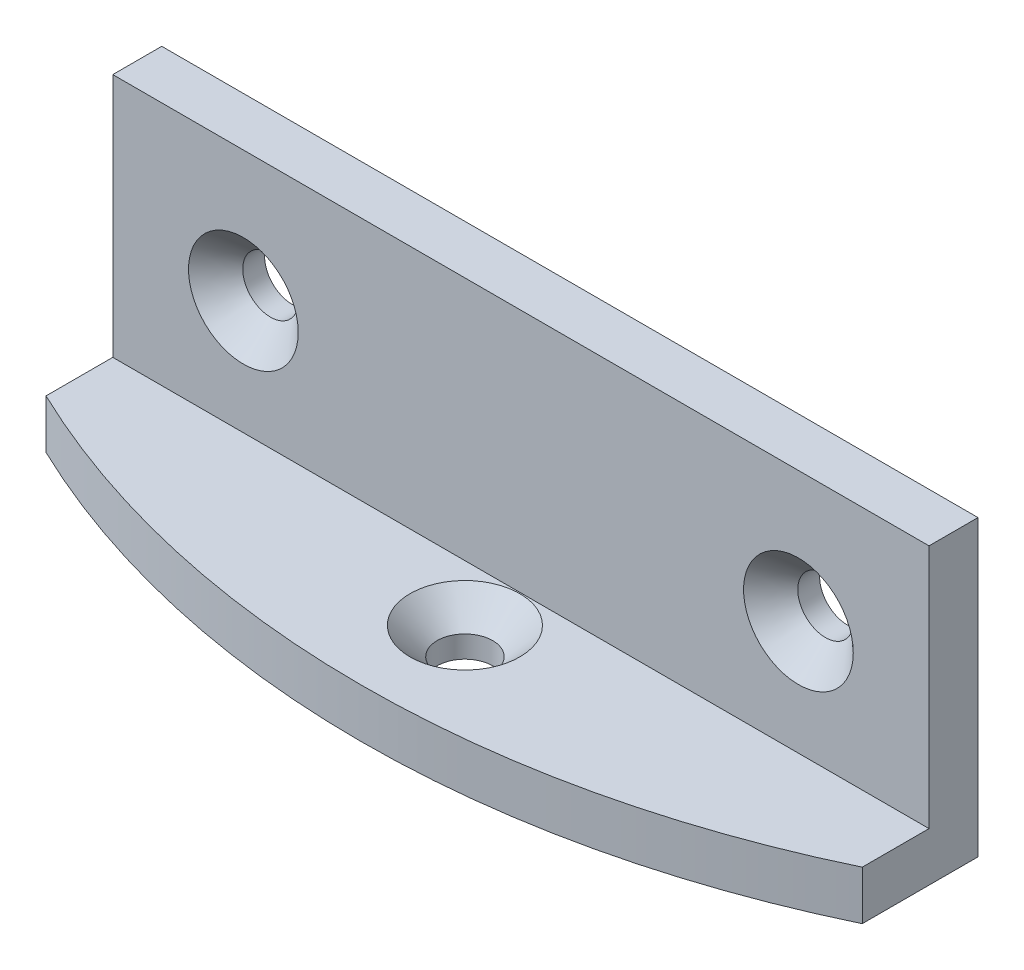
SolidWorks part; units mm, degrees
ref_plane "Plano frontal" through (0, 0, 0) normal (0, 0, 1) x (1, 0, 0)
ref_plane "Plano superior" through (0, 0, 0) normal (0, 1, 0) x (1, 0, 0)
ref_plane "Plano direito" through (0, 0, 0) normal (1, 0, 0) x (0, 0, -1)
sketch "Esboço2" plane through (0, 0, 0) normal (0, 1, 0) x (1, 0, 0)
  line L0 (-25, 0) -> (-25, -7.0901)
  line L1 (-25, 0) -> (25, 0)
  line L5 (25, 0) -> (25, -7.0901)
  arc A3 (-47.2548, 11.753) -> (-5.1654, -12.5473) centre (0, 45) ccw construction
  arc A4 (5.1654, -12.5473) -> (47.2548, 11.753) centre (0, 45) ccw construction
  arc A5 (-25, -7.0901) -> (25, -7.0901) centre (0, 45) ccw
  point P4 (0, 0)
  dimension "D1" = 50
extrude "Ressalto-extrusão1" add sketch "Esboço2" against normal blind 3 contours L1 L5 A5 L0
sketch "Esboço3" plane through (0, 0, 0) normal (0, 1, 0) x (1, 0, 0)
  line L1 (-25, 0) -> (25, 0)
  line L2 (-25, 0) -> (-25, -3)
  line L3 (-25, -3) -> (25, -3)
  line L4 (25, 0) -> (25, -3)
  line L5 (25, 0) -> (25, -7.0901) construction
  dimension "D1" = 3
extrude "Ressalto-extrusão2" add sketch "Esboço3" along normal blind 15
hole_wizard "Escareado para parafuso Allen sextavado escareado de M31" positions "Esboço4" profile "Esboço5" countersink size "M3" standard "ISO" end condition up to next
sketch "Esboço4" plane through (0, 0, 0) normal (0, 1, 0) x (1, 0, 0)
  point P0 (0, -6.4289)
sketch "Esboço5" plane through (0, 0, 6.4289) normal (1, 0, 0) x (0, 0, 1)
  line L0 (0, 0) -> (0, 3)
  line L1 (0, 3) -> (1.7, 3)
  line L2 (1.7, 3) -> (1.7, 1.66)
  line L3 (1.7, 1.66) -> (3.36, 0)
  line L5 (3.36, 0) -> (0, 0)
  line L6 (-1.7, 1.66) -> (-3.36, 0) construction
  line L11 (0, -6.35) -> (0, 107.95) construction
  dimension "Thru Hole Dia." = 3.4
  dimension "Thru Hole Depth" = 3
  dimension "Near C'Sink Dia." = 6.72
  dimension "Near C'Sink Angle" = 90
sketch "Esboço8" plane through (0, 0, 3) normal (0, 0, 1) x (1, 0, 0)
  line L0 (-25, 10) -> (-25, 4) construction
  line L1 (170, 10) -> (-170, 10) construction
  line L2 (170, 4) -> (-170, 4) construction
  line L3 (-25, 15) -> (-25, 0) construction
  line L4 (-25, 7) -> (25, 7) construction
  line L5 (25, 15) -> (25, 0) construction
hole_wizard "Escareado para parafuso Allen sextavado escareado de M33" positions "Esboço10" profile "Esboço11" countersink size "M3" standard "ISO" end condition up to next
sketch "Esboço10" plane through (0, 0, 3) normal (0, 0, 1) x (1, 0, 0)
  line L0 (-25, 7) -> (25, 7) construction
  line L1 (25, 15) -> (25, 0) construction
  point P0 (-17, 7)
  point P4 (17, 7)
  dimension "D1" = 8
  dimension "D2" = 8
sketch "Esboço11" plane through (-17, 7, 3) normal (1, 0, 0) x (0, -1, 0)
  line L0 (0, 0) -> (0, 3)
  line L1 (0, 3) -> (1.7, 3)
  line L2 (1.7, 3) -> (1.7, 1.66)
  line L3 (1.7, 1.66) -> (3.36, 0)
  line L5 (3.36, 0) -> (0, 0)
  line L6 (-1.7, 1.66) -> (-3.36, 0) construction
  line L11 (0, -6.35) -> (0, 107.95) construction
  dimension "Thru Hole Dia." = 3.4
  dimension "Thru Hole Depth" = 3
  dimension "Near C'Sink Dia." = 6.72
  dimension "Near C'Sink Angle" = 90
chamfer "Chanfro2" distance 2 angle 45 rebuild error yes
